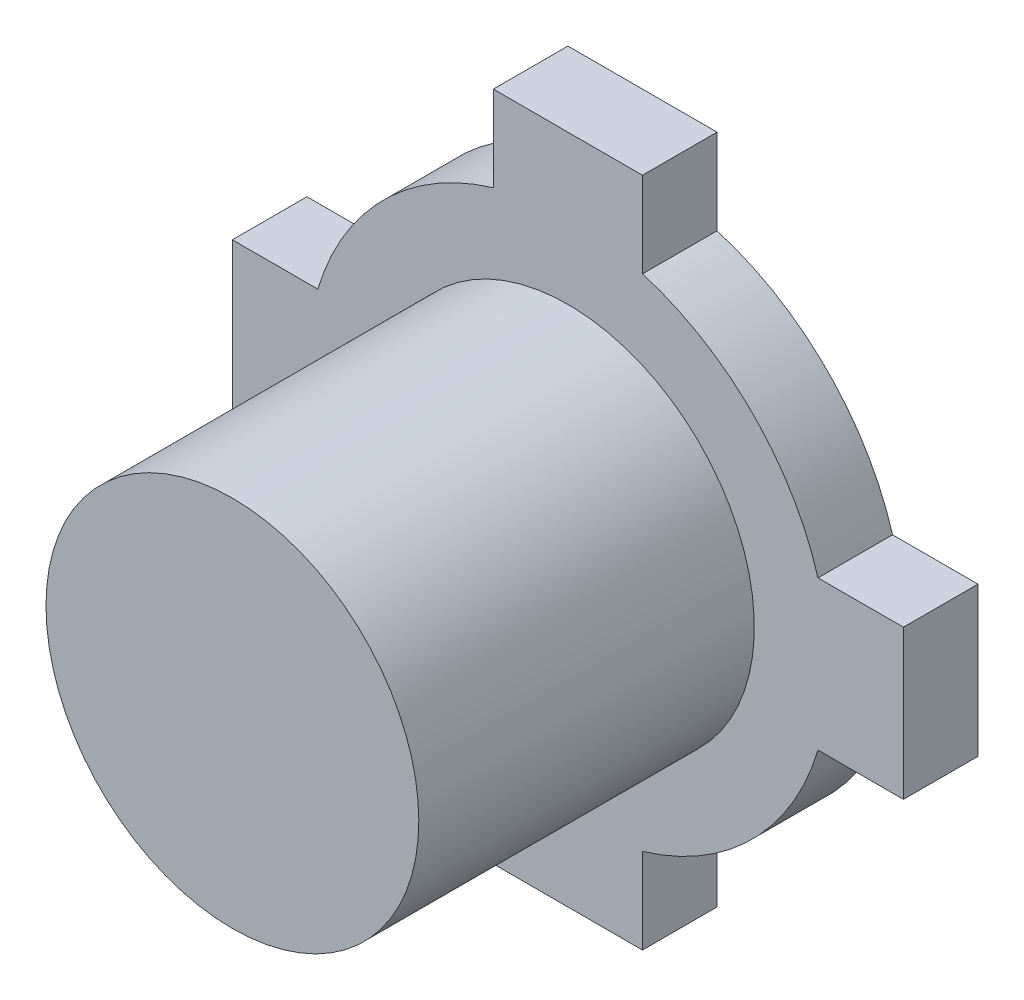
SolidWorks part; units mm, degrees
ref_plane "Front Plane" through (0, 0, 0) normal (0, 0, 1) x (1, 0, 0)
ref_plane "Top Plane" through (0, 0, 0) normal (0, 1, 0) x (1, 0, 0)
ref_plane "Right Plane" through (0, 0, 0) normal (1, 0, 0) x (0, 0, -1)
sketch "Sketch1" plane through (0, 0, 0) normal (0, 0, 1) x (1, 0, 0)
  circle A0 centre (0, 0) radius 2.5
  circle A1 centre (0, 0) radius 3 construction
  dimension "D1" = 0.5
extrude "Boss-Extrude1" add sketch "Sketch1" along normal blind 4.5
sketch "Sketch2" plane through (0, 0, 0) normal (0, 0, -1) x (-1, 0, 0)
  line L129 (-3.3541, 1) -> (-4.5, 1)
  line L130 (-4.5, 1) -> (-4.5, -1)
  line L131 (-4.5, -1) -> (-3.3541, -1)
  line L132 (-1, -3.3541) -> (-1, -4.5)
  line L133 (-1, -4.5) -> (1, -4.5)
  line L134 (1, -4.5) -> (1, -3.3541)
  line L135 (3.3541, -1) -> (4.5, -1)
  line L136 (4.5, -1) -> (4.5, 1)
  line L137 (4.5, 1) -> (3.3541, 1)
  line L138 (1, 3.3541) -> (1, 4.5)
  line L139 (1, 4.5) -> (-1, 4.5)
  line L140 (-1, 4.5) -> (-1, 3.3541)
  line L141 (-3.3541, 1) -> (-4.5, 1)
  line L142 (-4.5, 1) -> (-4.5, -1)
  line L143 (-4.5, -1) -> (-3.3541, -1)
  line L144 (-1, -3.3541) -> (-1, -4.5)
  line L145 (-1, -4.5) -> (1, -4.5)
  line L146 (1, -4.5) -> (1, -3.3541)
  line L147 (3.3541, -1) -> (4.5, -1)
  line L148 (4.5, -1) -> (4.5, 1)
  line L149 (4.5, 1) -> (3.3541, 1)
  line L150 (1, 3.3541) -> (1, 4.5)
  line L151 (1, 4.5) -> (-1, 4.5)
  line L152 (-1, 4.5) -> (-1, 3.3541)
  arc A35 (-1, 3.3541) -> (-3.3541, 1) centre (0, 0) ccw
  arc A36 (-3.3541, -1) -> (-1, -3.3541) centre (0, 0) ccw
  arc A37 (1, -3.3541) -> (3.3541, -1) centre (0, 0) ccw
  arc A38 (3.3541, 1) -> (1, 3.3541) centre (0, 0) ccw
  arc A39 (-1, 3.3541) -> (-3.3541, 1) centre (0, 0) ccw
  arc A40 (-3.3541, -1) -> (-1, -3.3541) centre (0, 0) ccw
  arc A41 (1, -3.3541) -> (3.3541, -1) centre (0, 0) ccw
  arc A42 (3.3541, 1) -> (1, 3.3541) centre (0, 0) ccw
  dimension "D1" = 0.5
extrude "Boss-Extrude2" add sketch "Sketch2" along normal blind 1
